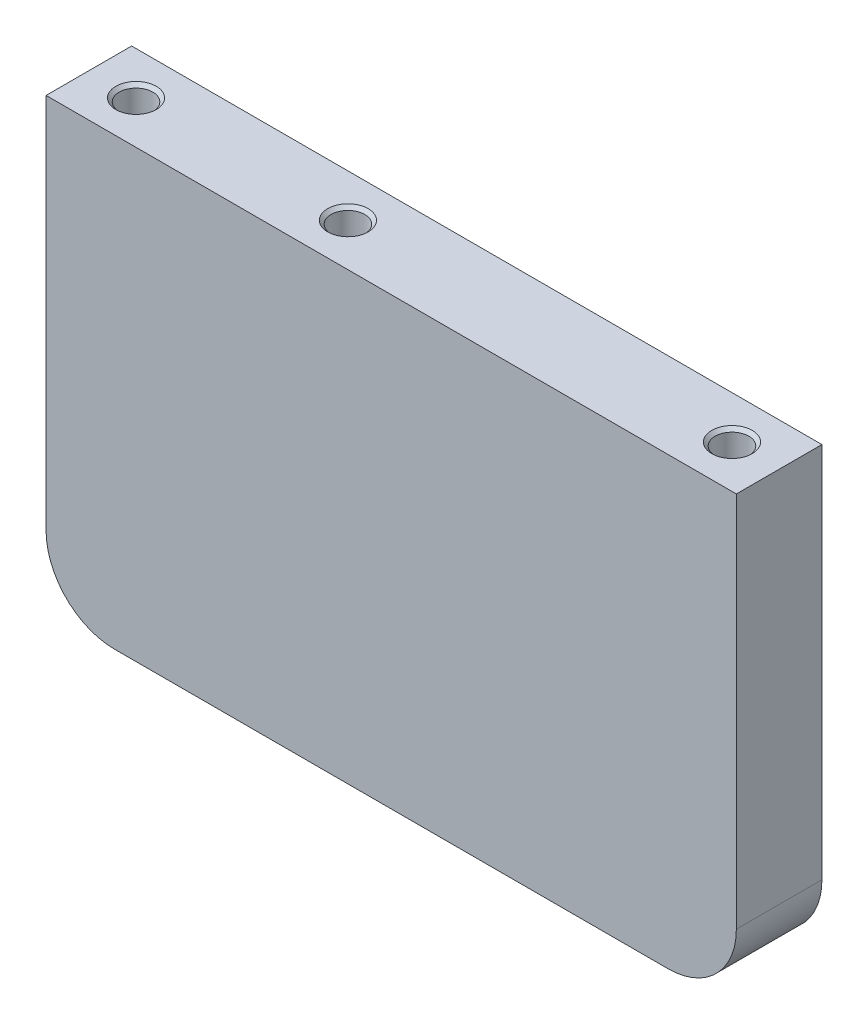
SolidWorks part; units mm, degrees
ref_plane "Front Plane" through (0, 0, 0) normal (0, 0, 1) x (1, 0, 0)
ref_plane "Top Plane" through (0, 0, 0) normal (0, 1, 0) x (1, 0, 0)
ref_plane "Right Plane" through (0, 0, 0) normal (1, 0, 0) x (0, 0, -1)
sketch "Sketch1" plane through (0, 0, 0) normal (0, 0, 1) x (1, 0, 0)
  line L10 (-33.225, 19.05) -> (18, 19.05)
  line L11 (-33.225, 19.05) -> (-33.225, -14)
  line L12 (-33.225, -14) -> (18, -14)
  line L13 (18, 19.05) -> (18, -14)
  circle A2 centre (0, 0) radius 11.1 construction
  circle A3 centre (-22.225, 0) radius 3.556 construction
  dimension "D2" = 7.112
  dimension "D5" = 19.05
  dimension "D6" = 11
  dimension "D3" = 22.225
  dimension "D1" = 22.2
  dimension "D8" = 51.225
  dimension "D4" = 14
  dimension "D7" = 18
extrude "Boss-Extrude1" add sketch "Sketch1" against normal blind 6.35
sketch "Sketch8" plane through (0, 19.05, 0) normal (0, 1, 0) x (1, 0, 0)
  line L0 (-33.225, 3.175) -> (18, 3.175) construction
  line L1 (-33.225, 6.35) -> (-33.225, 0) construction
  line L2 (18, 6.35) -> (18, 0) construction
  circle A1 centre (-29.725, 3.175) radius 1.25
  circle A2 centre (-14, 3.175) radius 1.25
  circle A3 centre (14.5, 3.175) radius 1.25
  dimension "D1" = 2.5
  dimension "D2" = 3.5
  dimension "D3" = 3.5
  dimension "D4" = 14
extrude "Cut-Extrude4" cut sketch "Sketch8" against normal blind 15
fillet "Fillet3" radius 5.08 2 edges at (18, -14, -3.175) (-33.225, -14, -3.175)
sketch "Sketch10" plane through (0, 0, -6.35) normal (0, 0, -1) x (-1, 0, 0)
  circle A0 centre (22.225, 0) radius 3.556 construction
  circle A1 centre (0, 0) radius 11.1 construction
  circle A2 centre (22.225, 0) radius 3.556
  circle A3 centre (0, 0) radius 11.1
extrude "Cut-Extrude5" cut sketch "Sketch10" against normal offset from surface (4.7625 mm away) 1.5875 up to face at (-7.6125, -1.6407, 0)
chamfer "Chamfer1" distance 0.25 angle 45 3 edges at (14.5, 19.05, -1.925) (-14, 19.05, -1.925) (-29.725, 19.05, -1.925)
